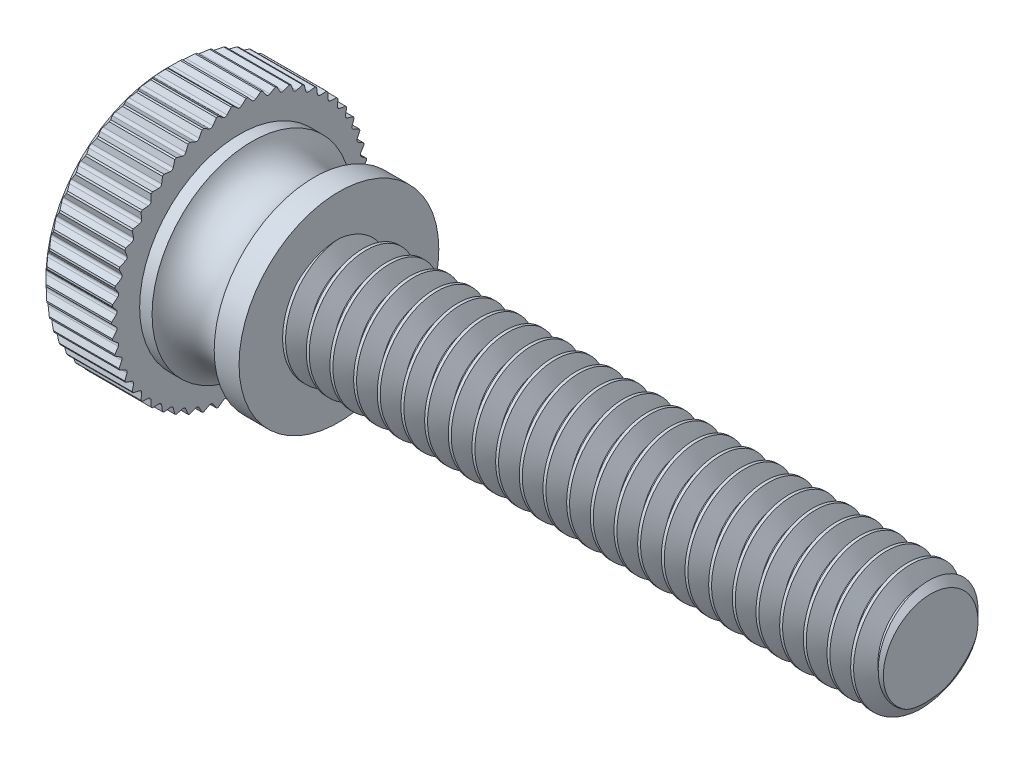
SolidWorks part; units mm, degrees
ref_plane "Front Plane" through (0, 0, 0) normal (0, 0, 1) x (1, 0, 0)
ref_plane "Top Plane" through (0, 0, 0) normal (0, 1, 0) x (1, 0, 0)
ref_plane "Right Plane" through (0, 0, 0) normal (1, 0, 0) x (0, 0, -1)
sketch "Sketch1" plane through (0, 0, 0) normal (0, 0, 1) x (1, 0, 0)
  line L0 (0, 0) -> (31.75, 0) construction
  line L1 (0, 0) -> (-9.271, 0) construction
  line L2 (-9.271, 6.858) -> (-9.271, -6.858) construction
  line L3 (31.75, 3.175) -> (31.75, -3.175) construction
  line L4 (0, 3.175) -> (0, -3.175) construction
  line L5 (-5.334, 5.3594) -> (-5.334, -5.3594) construction
  line L6 (-9.271, 6.858) -> (-5.334, 6.858) construction
  line L7 (31.75, 3.175) -> (30.48, 3.175) construction
  line L8 (-5.334, 5.3594) -> (0, 5.3594) construction
  line L9 (0, 3.175) -> (31.75, 3.175) construction
  line L10 (-9.271, -6.858) -> (-5.334, -6.858) construction
  line L11 (-5.334, -5.3594) -> (0, -5.3594) construction
  point P7 (31.75, 0)
  point P8 (0, 0)
  point P9 (-9.271, 0)
  point P16 (28.575, -3.175)
  point P17 (0, 0)
  point P21 (31.75, 0)
  point P22 (-9.271, 0)
  point P23 (-5.334, 0)
  dimension "Head Diameter" = 13.716
  dimension "Head Height" = 3.937
  dimension "Collar Diameter" = 10.7188
  dimension "Length" = 31.75
  dimension "Thread Pitch" = 1.27
  dimension "D2" = 3.175
  dimension "Overall Head Height" = 9.271
  dimension "Collar Height" = 5.334
  dimension "Screw Size Decimal Equivalent" = 6.35
sketch "Sketch2" plane through (0, 0, 0) normal (1, 0, 0) x (0, 0, -1)
  line L0 (0, 5.3594) -> (0, -5.3594) construction
  line L1 (-6.858, 0) -> (6.858, 0) construction
  line L2 (0, 6.858) -> (0, -6.858) construction
  circle A0 centre (0, 0) radius 6.858 construction
  circle A1 centre (0, 0) radius 5.3594 construction
  circle A2 centre (0, 0) radius 3.175 construction
  point P13 (0, -3.175)
  point P14 (3.175, 0)
  point P16 (0, 3.175)
  point P17 (-3.175, 0)
  point P18 (-5.3594, 0)
  point P19 (0, 5.3594)
  point P20 (5.3594, 0)
  point P21 (0, -5.3594)
  point P23 (0, -6.858)
  point P24 (6.858, 0)
  point P25 (0, 6.858)
  point P26 (-6.858, 0)
  point P27 (0, 0)
sketch "Sketch3" plane through (0, 0, 0) normal (0, 0, 1) x (1, 0, 0)
  line L0 (-9.271, 0) -> (-9.271, 6.858)
  line L1 (-9.271, 6.858) -> (-5.334, 6.858)
  line L2 (-5.334, 6.858) -> (-5.334, 5.3594)
  line L3 (-5.334, 5.3594) -> (-5.334, -5.3594) construction
  line L4 (-1.3335, 5.3594) -> (0, 5.3594)
  line L5 (0, -5.3594) -> (0, 5.3594) construction
  line L6 (0, 5.3594) -> (0, 3.175)
  line L7 (0, 3.175) -> (31.75, 3.175)
  line L8 (0, 3.175) -> (31.75, 3.175) construction
  line L10 (31.75, 3.175) -> (31.75, -3.175) construction
  line L11 (31.75, 3.175) -> (31.75, 0)
  line L12 (31.75, 0) -> (-9.271, 0)
  line L13 (-5.334, 5.3594) -> (-4.6673, 5.3594)
  line L14 (-5.334, 5.3594) -> (0, 5.3594) construction
  line L15 (-3.0004, 4.2875) -> (-3.0004, 5.3594) construction
  arc A1 (-4.6673, 5.3594) -> (-1.3335, 5.3594) centre (-3.0004, 6.1195) ccw
  dimension "D1" = 0.6667
  dimension "D2" = 1.3335
  dimension "D3" = 1.0719
revolve "Revolve1" add sketch "Sketch3" angle 360 about L0
chamfer "Chamfer1" distance 0.635 angle 45 1 edges at (31.75, 0, 3.175)
chamfer "Chamfer2" distance 0.4115 angle 45 1 edges at (-9.271, 0, 6.858)
split "Split1" trim tools "Right Plane" bodies to split 104 resulting bodies 105 106
sketch "Sketch4" plane through (31.75, 0, 0) normal (1, 0, 0) x (0, 0, -1)
  circle A0 centre (0, 0) radius 3.175
curve "Helix/Spiral1" pitch 1.27 height 33.02 turns 26
sketch "Sketch5" plane through (0, 0, 0) normal (0, 0, 1) x (1, 0, 0)
  line L0 (31.6706, 3.3125) -> (32.9406, 3.3125) construction
  line L1 (32.9406, 3.3125) -> (32.3056, 2.2126) construction
  line L2 (32.3056, 2.2126) -> (31.6706, 3.3125) construction
  line L3 (31.7103, 3.2437) -> (32.9009, 3.2437) construction
  line L4 (31.75, 3.175) -> (32.8612, 3.175) construction
  line L5 (32.2263, 2.3501) -> (32.385, 2.3501) construction
  line L6 (32.3056, 2.2126) -> (32.3056, 2.3501) construction
  line L7 (32.3056, 3.175) -> (32.3056, 3.3125) construction
  line L8 (31.7103, 3.2437) -> (32.9009, 3.2437)
  line L9 (32.9009, 3.2437) -> (32.385, 2.3501)
  line L10 (32.385, 2.3501) -> (32.2263, 2.3501)
  line L11 (32.2263, 2.3501) -> (31.7103, 3.2437)
  point P12 (32.3056, 3.2437)
  dimension "D1" = 1.27
  dimension "D2" = 0.1588
sweep "Cut-Sweep1" cut profiles "Sketch5" path "Helix/Spiral1"
sketch "Sketch6" plane through (0, 0, 0) normal (1, 0, 0) x (0, 0, -1)
  circle A0 centre (0, 0) radius 3.175
  circle A1 centre (0, 0) radius 3.175 construction
extrude "Boss-Extrude1" add sketch "Sketch6" against normal through all draft 60
sketch "Sketch7" plane through (-9.271, 0, 0) normal (-1, 0, 0) x (0, 0, 1)
  line L0 (0, 0) -> (0.3594, 6.858) construction
  line L1 (0, 3.175) -> (0, -3.175) construction
  line L2 (0.3594, 6.858) -> (-0.3594, 6.858) construction
  line L3 (-0.3594, 6.858) -> (0, 0) construction
  line L4 (0, 0) -> (0, 6.858) construction
  line L5 (-0.6374, 7.112) -> (0.6374, 7.112)
  line L6 (0.6374, 7.112) -> (0, 6.5296) construction
  line L7 (0, 6.5296) -> (-0.6374, 7.112) construction
  line L8 (0, 6.5296) -> (0, 7.112) construction
  line L9 (-0.6374, 7.112) -> (-0.1029, 6.6236)
  line L10 (0.1029, 6.6236) -> (0.6374, 7.112)
  line L11 (0.1029, 6.6236) -> (-0.1029, 6.6236) construction
  line L12 (0, 6.858) -> (0, -6.858) construction
  circle A0 centre (0, 0) radius 6.858 construction
  arc A1 (-0.1029, 6.6236) -> (0.1029, 6.6236) centre (0, 6.7362) ccw
  point P16 (0, 6.5837)
  dimension "D1" = 6
  dimension "D2" = 0.2743
  dimension "D3" = 0.2057
  dimension "D4" = 0.254
extrude "Cut-Extrude1" cut sketch "Sketch7" against normal up to vertex (9.271 mm away) up to point (0, 6.858, 0)
pattern_circular "CirPattern1" count 54 over 360 about axis through (0, 0, 0) along (1, 0, 0) of "Cut-Extrude1"
equation "\"D2@Sketch1\"=\"Thread Pitch@Sketch1\"*2.5"
equation "\"D1@Sketch3\"=\"Collar Height@Sketch1\"*.125"
equation "\"D2@Sketch3\"=\"Collar Height@Sketch1\"*.25"
equation "\"D3@Sketch3\"=\"Collar Diameter@Sketch1\"*.1"
equation "\"D1@Chamfer1\"=\"Thread Pitch@Sketch1\"*.5"
equation "\"D1@Chamfer2\"=\"Head Diameter@Sketch1\"*.03"
equation "\"D4@Helix/Spiral1\"=\"Thread Pitch@Sketch1\""
equation "\"D3@Helix/Spiral1\"=\"Length@Sketch1\"+\"Thread Pitch@Sketch1\""
equation "\"D2@Sketch5\"=\"D1@Sketch5\"*.125"
equation "\"D1@Sketch5\"=\"Thread Pitch@Sketch1\""
equation "\"D2@Sketch7\"=\"Head Diameter@Sketch1\"*.02"
equation "\"D3@Sketch7\"=\"Head Diameter@Sketch1\"*.015"
equation "\"D1@CirPattern1\"=(360/\"D1@Sketch7\")*.9"
